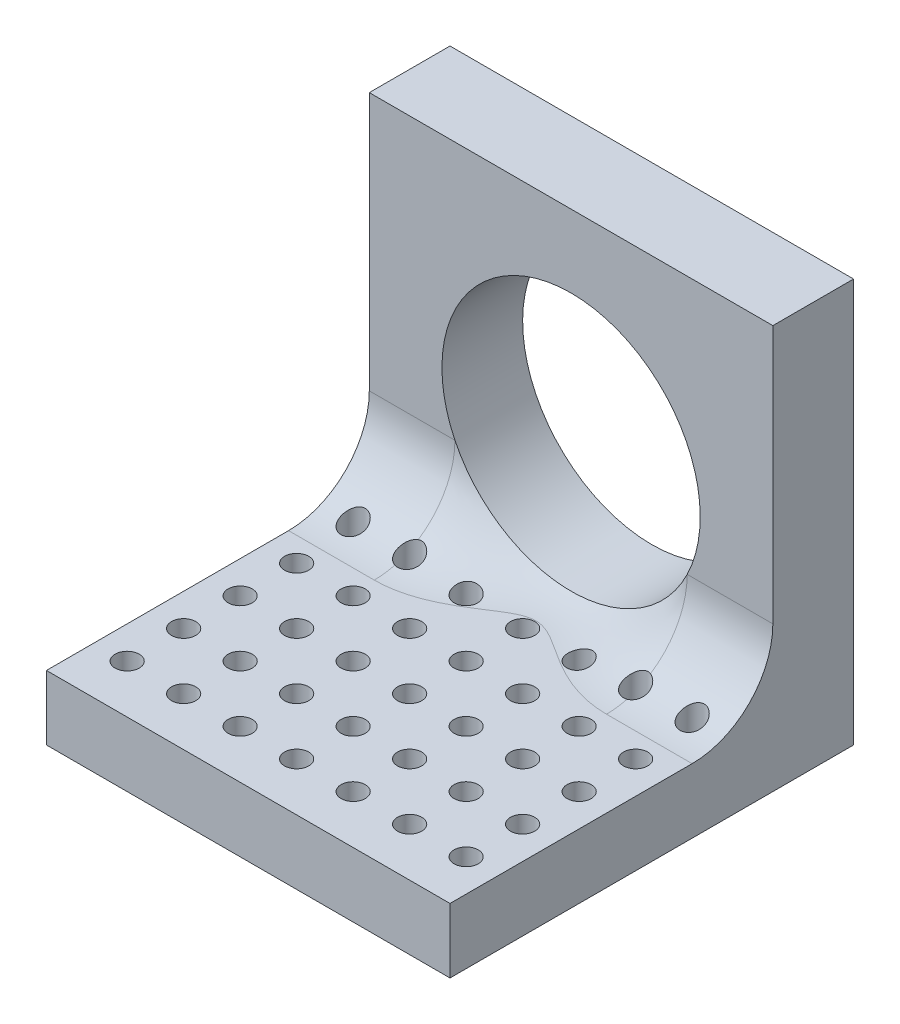
SolidWorks part; units mm, degrees
ref_plane "Plano frontal" through (0, 0, 0) normal (0, 0, 1) x (1, 0, 0)
ref_plane "Plano superior" through (0, 0, 0) normal (0, 1, 0) x (1, 0, 0)
ref_plane "Plano direito" through (0, 0, 0) normal (1, 0, 0) x (0, 0, -1)
sketch "Esboço1" plane through (0, 0, 0) normal (0, 0, 1) x (1, 0, 0)
  line L0 (0, 0) -> (50, -50) construction
  line L1 (0, 0) -> (50, 0)
  line L2 (0, 0) -> (0, -50)
  line L3 (0, -50) -> (50, -50)
  line L4 (50, 0) -> (50, -50)
  line L5 (0, -50) -> (50, 0) construction
  circle A0 centre (25, -25) radius 16
  dimension "D3" = 32
  dimension "D1" = 50
  dimension "D2" = 50
extrude "Ressalto-extrusão1" add sketch "Esboço1" along normal blind 10
sketch "Esboço2" plane through (0, 0, 0) normal (0, 0, 1) x (1, 0, 0)
  line L0 (50, -50) -> (50, 0) construction
  line L1 (0, -50) -> (50, -50)
  line L2 (0, -50) -> (0, -42)
  line L3 (0, -42) -> (50, -42)
  line L4 (50, -50) -> (50, -42)
  dimension "D1" = 8
extrude "Ressalto-extrusão2" add sketch "Esboço2" along normal blind 50
sketch "Esboço3" plane through (0, 0, 0) normal (0, 1, 0) x (1, 0, 0)
  line L0 (25, 0) -> (25, -50) construction
  line L1 (50, 0) -> (0, 0) construction
  line L2 (50, -50) -> (0, -50) construction
  line L3 (25, -50) -> (0, -50) construction
  line L4 (0, -50) -> (0, -10) construction
  line L5 (0, -50) -> (0, -30) construction
  line L6 (0, -30) -> (50, -30) construction
  line L7 (50, -50) -> (50, -10) construction
  line L8 (25, -30) -> (35, -30) construction
  line L9 (25, -30) -> (32, -30) construction
  line L10 (25, -30) -> (18, -30) construction
  line L11 (25, -30) -> (25, -37) construction
  line L12 (25, -30) -> (32, -30) construction
  line L13 (25, -30) -> (18, -30) construction
  circle A0 centre (25, -30) radius 1.5
  circle A1 centre (32, -30) radius 1.5
  circle A2 centre (39, -30) radius 1.5
  circle A3 centre (46, -30) radius 1.5
  circle A4 centre (32, -23) radius 1.5
  circle A5 centre (39, -23) radius 1.5
  circle A6 centre (46, -23) radius 1.5
  circle A7 centre (32, -16) radius 1.5
  circle A8 centre (39, -16) radius 1.5
  circle A9 centre (46, -16) radius 1.5
  circle A10 centre (25, -23) radius 1.5
  circle A11 centre (25, -16) radius 1.5
  circle A12 centre (18, -30) radius 1.5
  circle A13 centre (11, -30) radius 1.5
  circle A14 centre (4, -30) radius 1.5
  circle A15 centre (18, -37) radius 1.5
  circle A16 centre (11, -37) radius 1.5
  circle A17 centre (4, -37) radius 1.5
  circle A18 centre (18, -44) radius 1.5
  circle A19 centre (11, -44) radius 1.5
  circle A20 centre (4, -44) radius 1.5
  circle A21 centre (25, -37) radius 1.5
  circle A22 centre (25, -44) radius 1.5
  circle A23 centre (32, -30) radius 1.5
  circle A24 centre (39, -30) radius 1.5
  circle A25 centre (46, -30) radius 1.5
  circle A26 centre (32, -37) radius 1.5
  circle A27 centre (39, -37) radius 1.5
  circle A28 centre (46, -37) radius 1.5
  circle A29 centre (32, -44) radius 1.5
  circle A30 centre (39, -44) radius 1.5
  circle A31 centre (46, -44) radius 1.5
  circle A32 centre (25, -37) radius 1.5
  circle A33 centre (25, -44) radius 1.5
  circle A34 centre (18, -30) radius 1.5
  circle A35 centre (11, -30) radius 1.5
  circle A36 centre (4, -30) radius 1.5
  circle A37 centre (18, -23) radius 1.5
  circle A38 centre (11, -23) radius 1.5
  circle A39 centre (4, -23) radius 1.5
  circle A40 centre (18, -16) radius 1.5
  circle A41 centre (11, -16) radius 1.5
  circle A42 centre (4, -16) radius 1.5
  circle A43 centre (25, -23) radius 1.5
  circle A44 centre (25, -16) radius 1.5
  dimension "D1" = 3
  dimension "D4" = 10
  dimension "D5" = 7
  dimension "D8" = 7
  dimension "D9" = 7
  dimension "D12" = 7
  dimension "D15" = 7
  dimension "D6" = 4
  dimension "D7" = 3
  dimension "D10" = 4
  dimension "D11" = 3
  dimension "D2" = 4
  dimension "D3" = 3
  dimension "D13" = 4
  dimension "D14" = 3
extrude "Corte-extrusão1" cut sketch "Esboço3" against normal blind 101 contours A17 | A20 | A19 | A18 | A22 | A29 | A30 | A31 | A28 | A27 | A26 | A21 | A15 | A16 | A14 | A13 | A12 | A1 | A0 | A2 | A3 | A6 | A5 | A4 | A37 | A10 | A38 | A39 | A42 | A41 | A40 | A11 | A7 | A8 | A9 region at (4, 0, 37)
fillet "Filete1" radius 10 1 edges at (25, -42, 10)
